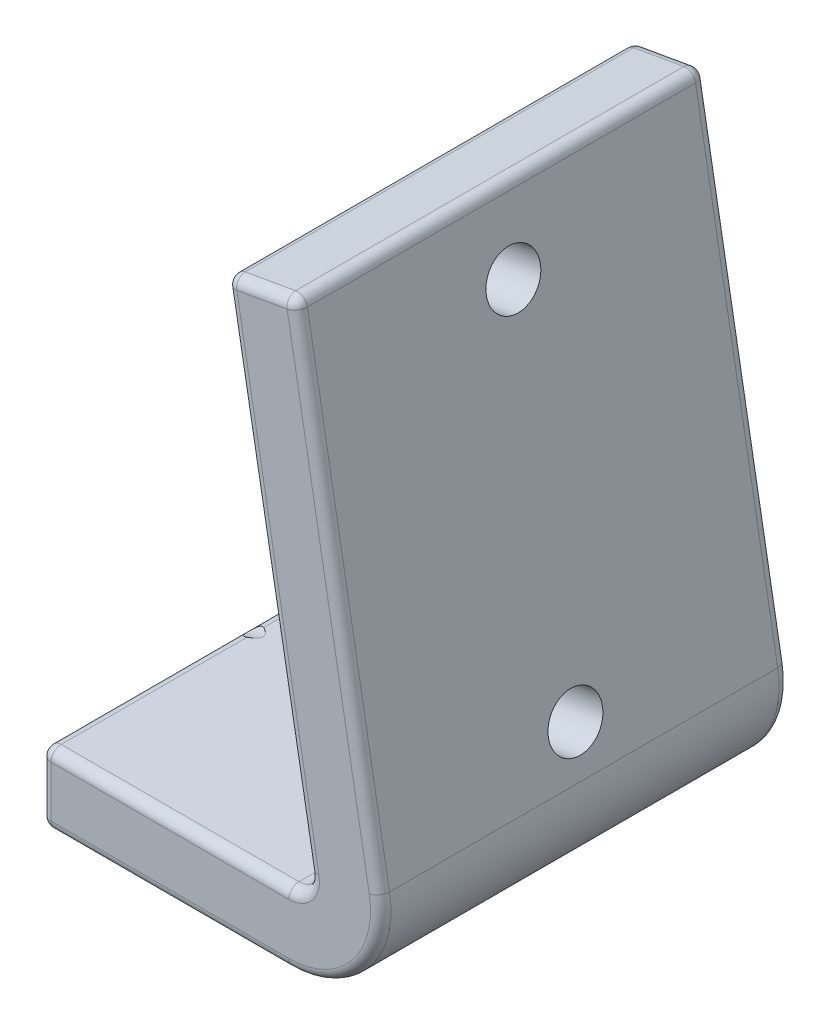
SolidWorks part; units mm, degrees
ref_plane "Front Plane" through (0, 0, 0) normal (0, 0, 1) x (1, 0, 0)
ref_plane "Top Plane" through (0, 0, 0) normal (0, 1, 0) x (1, 0, 0)
ref_plane "Right Plane" through (0, 0, 0) normal (1, 0, 0) x (0, 0, -1)
ref_axis "Axis1" through (0, 0, -88.99) along (0, 0, 1)
ref_plane "Plane1" through (0, 0, 0) normal (0.9848, 0.1736, 0) x (0, 0, 1)
sketch "Sketch2" plane through (0, 0, 0) normal (0, 0, 1) x (1, 0, 0)
  line L0 (0, 0) -> (-35, 0)
  line L1 (55, 0) -> (-55, 0) construction
  line L2 (-35, 0) -> (-35, 7)
  line L3 (-35, 7) -> (-8.3423, 7)
  line L4 (-8.3423, 7) -> (-16.9652, 55.9033)
  line L5 (-16.9652, 55.9033) -> (-10.0716, 57.1188)
  line L6 (11.0615, -62.733) -> (-11.0615, 62.733) construction
  line L7 (-10.0716, 57.1188) -> (0, 0)
  dimension "D1" = 35
  dimension "D2" = 58
  dimension "D3" = 7
extrude "Boss-Extrude1" add sketch "Sketch2" along normal mid plane 40
fillet "Fillet2" radius 2 1 edges at (-8.3423, 7, 0)
fillet "Fillet3" radius 9 1 edges at (0, 0, 0)
fillet "Fillet1" radius 1 20 edges at (-22.8629, 0, 20) (-22.8629, 7, 20) (-12.8607, 32.6253, 20) (-5.9671, 33.8408, 20) (-35, 7, 0) (-35, 3.5, 20) (-35, 0, 0) (-35, 3.5, -20) (-10.0716, 57.1188, 0) (-13.5184, 56.5111, 20) (-16.9652, 55.9033, 0) (-13.5184, 56.5111, -20) (-9.1937, 7.7144, 20) (-3.8314, 3.2149, 20) (-12.8607, 32.6253, -20) (-9.1937, 7.7144, -20) (-22.8629, 7, -20) (-22.8629, 0, -20) (-3.8314, 3.2149, -20) (-5.9671, 33.8408, -20)
hole_wizard "Hole1" positions "Sketch5" profile "Sketch6" legacy end condition through all
sketch "Sketch5" plane through (0, 0, 0) normal (0.9848, 0.1736, 0) x (0, 0, -1)
  line L7 (0, 15.3162) -> (0, 50.3162) construction
  line L9 (0, 55) -> (0, -55) construction
  point P7 (0, 50.3162)
  point P9 (0, 15.3162)
  point P34 (0, 51.0999)
  point P37 (0, 50.3162)
  dimension "D1" = 35
sketch "Sketch6" plane through (-8.7373, 49.5518, 0) normal (0, 0, 1) x (-0.1736, 0.9848, 0)
  line L0 (0, 0) -> (0, 34.4683)
  line L1 (0, 34.4683) -> (2.65, 34.4683)
  line L2 (2.65, 34.4683) -> (2.65, 0)
  line L3 (2.65, 0) -> (0, 0)
  line L4 (0, 110) -> (0, -10) construction
  dimension "Diameter" = 5.3
  dimension "Depth" = 34.4683
